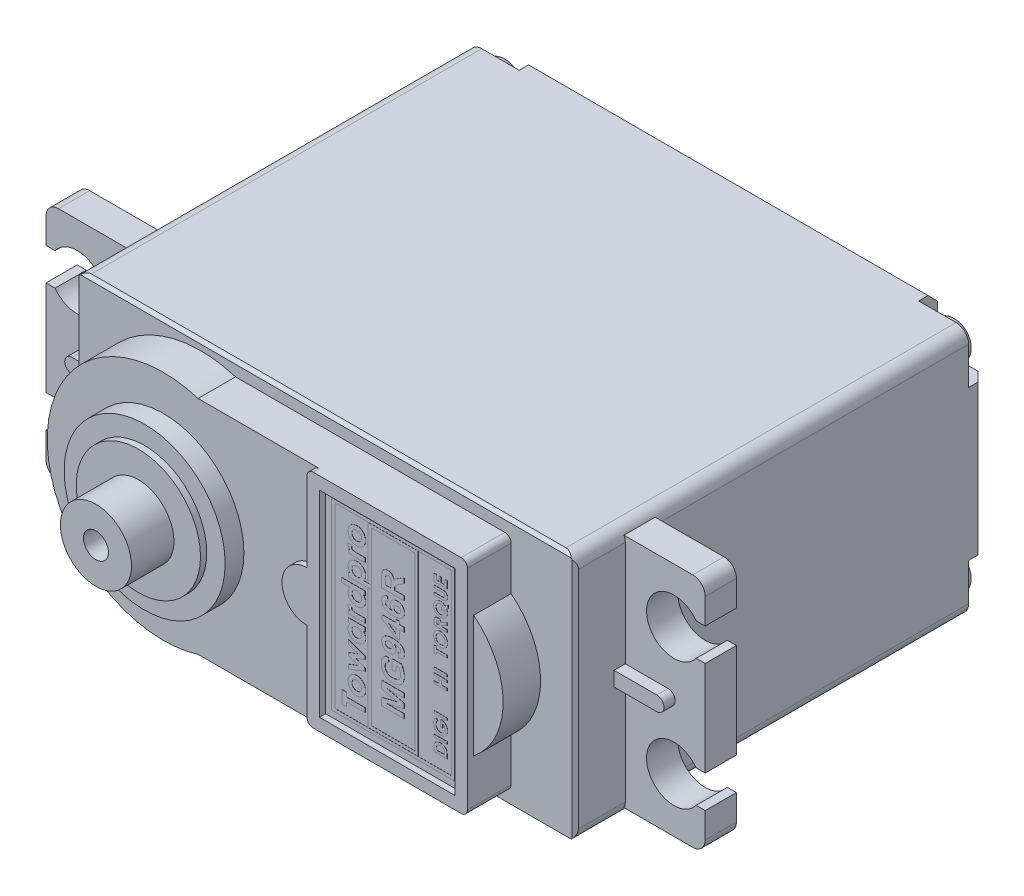
SolidWorks part; units mm, degrees
ref_plane "Front Plane" through (0, 0, 0) normal (0, 0, 1) x (1, 0, 0)
ref_plane "Top Plane" through (0, 0, 0) normal (0, 1, 0) x (1, 0, 0)
ref_plane "Right Plane" through (0, 0, 0) normal (1, 0, 0) x (0, 0, -1)
ref_plane "Plane1" through (0, -10, 0) normal (0, -1, 0) x (1, 0, 0)
sketch "Sketch1" plane through (0, -10, 0) normal (0, -1, 0) x (1, 0, 0)
  line L0 (-20, 16.5) -> (-20, -16.5)
  line L1 (-20, -16.5) -> (20, -16.5)
  line L2 (20, -16.5) -> (20, 16.5)
  line L3 (20, 16.5) -> (-20, 16.5)
extrude "Boss-Extrude1" add sketch "Sketch1" against normal blind 20
sketch "Sketch2" plane through (0, 0, 16.5) normal (0, 0, 1) x (1, 0, 0)
  line L0 (14.8541, 8.875) -> (14.8541, -8.875)
  line L1 (14.8541, -8.875) -> (-7.2207, -8.875)
  line L2 (-7.2207, 8.875) -> (14.8541, 8.875)
  arc A0 (-7.2207, -8.875) -> (-7.2207, 8.875) centre (-10, 0) cw
extrude "Boss-Extrude2" add sketch "Sketch2" along normal blind 3
sketch "Sketch3" plane through (0, 0, 19.5) normal (0, 0, 1) x (1, 0, 0)
  line L0 (2.0041, 8.875) -> (14.8541, 8.875)
  line L1 (14.8541, 8.875) -> (14.8541, -8.875)
  line L2 (14.8541, -8.875) -> (2.0041, -8.875)
  line L3 (2.0041, -8.875) -> (2.0041, 8.875)
extrude "Boss-Extrude3" add sketch "Sketch3" along normal blind 0.5
sketch "Sketch4" plane through (0, 0, 19.5) normal (0, 0, 1) x (1, 0, 0)
  line L0 (2.0041, 2) -> (2.0041, -2)
  arc A0 (2.0041, -2) -> (2.0041, 2) centre (2.0041, 0) cw
extrude "Boss-Extrude4" add sketch "Sketch4" along normal blind 0.5
sketch "Sketch5" plane through (-20, 0, 0) normal (-1, 0, 0) x (0, 0, 1)
  line L0 (10, 9.45) -> (12.5, 9.45)
  line L1 (12.5, 9.45) -> (12.5, -9.45)
  line L2 (12.5, -9.45) -> (10, -9.45)
  line L3 (10, -9.45) -> (10, 9.45)
extrude "Boss-Extrude5" add sketch "Sketch5" along normal blind 6.4
sketch "Sketch6" plane through (0, 0, 10) normal (0, 0, -1) x (-1, 0, 0)
  line L0 (26.4, 6.4) -> (25.6748, 6.4)
  line L1 (25.6748, 3.8) -> (26.4, 3.8)
  line L2 (26.4, 3.8) -> (26.4, 6.4)
  arc A0 (25.6748, 6.4) -> (25.6748, 3.8) centre (23.9, 5.1) cw
extrude "Cut-Extrude1" cut sketch "Sketch6" against normal through all
sketch "Sketch7" plane through (0, 0, 10) normal (0, 0, -1) x (-1, 0, 0)
  line L0 (26.4, -3.8) -> (25.6748, -3.8)
  line L1 (25.6748, -6.4) -> (26.4, -6.4)
  line L2 (26.4, -6.4) -> (26.4, -3.8)
  arc A0 (25.6748, -3.8) -> (25.6748, -6.4) centre (23.9, -5.1) cw
extrude "Cut-Extrude2" cut sketch "Sketch7" against normal through all
sketch "Sketch8" plane through (20, 0, 0) normal (1, 0, 0) x (0, 0, -1)
  line L0 (-10, -9.45) -> (-12.5, -9.45)
  line L1 (-12.5, -9.45) -> (-12.5, 9.45)
  line L2 (-12.5, 9.45) -> (-10, 9.45)
  line L3 (-10, 9.45) -> (-10, -9.45)
extrude "Boss-Extrude6" add sketch "Sketch8" along normal blind 6.4
sketch "Sketch9" plane through (0, 0, 12.5) normal (0, 0, 1) x (1, 0, 0)
  line L0 (26.4, 3.8) -> (26.4, 6.4)
  line L1 (26.4, 6.4) -> (25.6748, 6.4)
  line L2 (25.6748, 3.8) -> (26.4, 3.8)
  arc A0 (25.6748, 6.4) -> (25.6748, 3.8) centre (23.9, 5.1) cw
extrude "Cut-Extrude3" cut sketch "Sketch9" against normal through all
sketch "Sketch10" plane through (0, 0, 12.5) normal (0, 0, 1) x (1, 0, 0)
  line L0 (26.4, -6.4) -> (26.4, -3.8)
  line L1 (26.4, -3.8) -> (25.6748, -3.8)
  line L2 (25.6748, -6.4) -> (26.4, -6.4)
  arc A0 (25.6748, -3.8) -> (25.6748, -6.4) centre (23.9, -5.1) cw
extrude "Cut-Extrude4" cut sketch "Sketch10" against normal through all
sketch "Sketch11" plane through (0, 0, 12.5) normal (0, 0, 1) x (1, 0, 0)
  line L0 (-23.42, 0.58) -> (-20, 0.58)
  line L1 (-20, 0.58) -> (-20, -0.58)
  line L2 (-20, -0.58) -> (-23.42, -0.58)
  arc A0 (-23.42, -0.58) -> (-23.42, 0.58) centre (-23.42, 0) cw
extrude "Boss-Extrude7" add sketch "Sketch11" along normal blind 0.9
sketch "Sketch12" plane through (0, 10, 0) normal (0, 1, 0) x (-1, 0, 0)
  line L0 (-16, -16.5) -> (-16, -15)
  line L1 (-16, -15) -> (-20, -15)
  line L2 (-20, -15) -> (-20, -16.5)
  line L3 (-20, -16.5) -> (-16, -16.5)
extrude "Cut-Extrude5" cut sketch "Sketch12" against normal blind 4
sketch "Sketch13" plane through (-20, 0, 0) normal (-1, 0, 0) x (0, 0, 1)
  line L0 (-16.5, 6) -> (-15, 6)
  line L1 (-15, 6) -> (-15, 10)
  line L2 (-15, 10) -> (-16.5, 10)
  line L3 (-16.5, 10) -> (-16.5, 6)
extrude "Cut-Extrude6" cut sketch "Sketch13" against normal blind 4
sketch "Sketch14" plane through (-20, 0, 0) normal (-1, 0, 0) x (0, 0, 1)
  line L0 (-16.5, -10) -> (-15, -10)
  line L1 (-15, -10) -> (-15, -6)
  line L2 (-15, -6) -> (-16.5, -6)
  line L3 (-16.5, -6) -> (-16.5, -10)
extrude "Cut-Extrude7" cut sketch "Sketch14" against normal blind 4
sketch "Sketch15" plane through (0, -10, 0) normal (0, -1, 0) x (1, 0, 0)
  line L0 (20, -16.5) -> (20, -15)
  line L1 (20, -15) -> (16, -15)
  line L2 (16, -15) -> (16, -16.5)
  line L3 (16, -16.5) -> (20, -16.5)
extrude "Cut-Extrude8" cut sketch "Sketch15" against normal blind 4
sketch "Sketch16" plane through (0, 0, 12.5) normal (0, 0, 1) x (1, 0, 0)
  line L0 (23.42, -0.58) -> (20, -0.58)
  line L1 (20, -0.58) -> (20, 0.58)
  line L2 (20, 0.58) -> (23.42, 0.58)
  arc A0 (23.42, 0.58) -> (23.42, -0.58) centre (23.42, 0) cw
extrude "Boss-Extrude8" add sketch "Sketch16" along normal blind 0.9
sketch "Sketch17" plane through (0, 0, 16.5) normal (0, 0, 1) x (1, 0, 0)
  line L0 (14.8541, -4.875) -> (14.8541, 4.875)
  arc A0 (14.8541, 4.875) -> (14.8541, -4.875) centre (11, 0) cw
extrude "Boss-Extrude9" add sketch "Sketch17" along normal blind 3
sketch "Sketch18" plane through (0, 0, 20) normal (0, 0, 1) x (1, 0, 0)
  line L0 (13.8541, 7.875) -> (3.0041, 7.875)
  line L1 (3.0041, 7.875) -> (3.0041, -7.875)
  line L2 (3.0041, -7.875) -> (13.8541, -7.875)
  line L3 (13.8541, -7.875) -> (13.8541, 7.875)
extrude "Cut-Extrude9" cut sketch "Sketch18" against normal blind 0.5
sketch "Sketch19" plane through (0, 0, 0) normal (0, 1, 0) x (1, 0, 0)
  line L0 (-3.55, -19.5) -> (-10, -19.5)
  line L1 (-10, -19.5) -> (-10, -24.9)
  line L2 (-10, -24.9) -> (-7.15, -24.9)
  line L3 (-7.15, -24.9) -> (-7.15, -21.5)
  line L4 (-7.15, -21.5) -> (-5.025, -21.5)
  line L5 (-5.025, -21.5) -> (-5.025, -21)
  line L6 (-5.025, -21) -> (-3.55, -21)
  line L7 (-3.55, -21) -> (-3.55, -19.5)
  line L8 (-10, -19.5) -> (-10, -24.9) construction
revolve "Revolve1" add sketch "Sketch19" angle 360 about L8 reverse direction yes
ref_plane "Plane2" through (0, -5.1, 0) normal (0, -1, 0) x (1, 0, 0)
sketch "Sketch20" plane through (0, -5.1, 0) normal (0, -1, 0) x (1, 0, 0)
  line L0 (26.1, 12.5) -> (23.9, 12.5)
  line L1 (23.9, 12.5) -> (23.9, 10)
  line L2 (23.9, 10) -> (26.1, 10)
  line L3 (26.1, 10) -> (26.1, 12.5)
  line L4 (23.9, 12.5) -> (23.9, 10) construction
revolve "Cut-Revolve1" cut sketch "Sketch20" angle 360 about L4 reverse direction yes
ref_plane "Plane3" through (0, 5.1, 0) normal (0, -1, 0) x (1, 0, 0)
sketch "Sketch21" plane through (0, 5.1, 0) normal (0, -1, 0) x (1, 0, 0)
  line L0 (26.1, 12.5) -> (23.9, 12.5)
  line L1 (23.9, 12.5) -> (23.9, 10)
  line L2 (23.9, 10) -> (26.1, 10)
  line L3 (26.1, 10) -> (26.1, 12.5)
  line L4 (23.9, 12.5) -> (23.9, 10) construction
revolve "Cut-Revolve2" cut sketch "Sketch21" angle 360 about L4 reverse direction yes
sketch "Sketch22" plane through (0, 5.1, 0) normal (0, -1, 0) x (1, 0, 0)
  line L0 (-21.7, 12.5) -> (-23.9, 12.5)
  line L1 (-23.9, 12.5) -> (-23.9, 10)
  line L2 (-23.9, 10) -> (-21.7, 10)
  line L3 (-21.7, 10) -> (-21.7, 12.5)
  line L4 (-23.9, 12.5) -> (-23.9, 10) construction
revolve "Cut-Revolve3" cut sketch "Sketch22" angle 360 about L4 reverse direction yes
sketch "Sketch23" plane through (0, -5.1, 0) normal (0, -1, 0) x (1, 0, 0)
  line L0 (-21.7, 12.5) -> (-23.9, 12.5)
  line L1 (-23.9, 12.5) -> (-23.9, 10)
  line L2 (-23.9, 10) -> (-21.7, 10)
  line L3 (-21.7, 10) -> (-21.7, 12.5)
  line L4 (-23.9, 12.5) -> (-23.9, 10) construction
  dimension "D1" = 2.2
revolve "Cut-Revolve4" cut sketch "Sketch23" angle 360 about L4 reverse direction yes
hole_wizard "Ø2.0 (2) Diameter Hole1" positions "Sketch25" profile "Sketch24" hole size "Ø2.0" standard "ANSI Metric"
sketch "Sketch25" plane through (0, 0, 24.9) normal (0, 0, 1) x (1, 0, 0)
  point P0 (-10, 0)
sketch "Sketch24" plane through (-10, 0, 24.9) normal (1, 0, 0) x (0, -1, 0)
  line L0 (0, 0) -> (0, 3.4)
  line L1 (0, 3.4) -> (1, 3.4)
  line L2 (1, 3.4) -> (1, 0)
  line L5 (1, 0) -> (0, 0)
  line L10 (0, 3.4) -> (-1, 3.4) construction
  line L11 (0, -6.35) -> (0, 107.95) construction
  dimension "Hole Dia." = 2
  dimension "Hole Depth" = 3.4
  dimension "Drill Angle" = 180
hole_wizard "Ø1.8 (1.8) Diameter Hole1" positions "Sketch27" profile "Sketch26" hole size "Ø1.8" standard "ANSI Metric"
sketch "Sketch27" plane through (0, 0, -15) normal (0, 0, -1) x (-1, 0, 0)
  point P0 (-18, 8)
  point P1 (18, 8)
  point P2 (18, -8)
  point P3 (-18, -8)
sketch "Sketch26" plane through (18, 8, -15) normal (1, 0, 0) x (0, 1, 0)
  line L0 (0, 0) -> (0, 8.5408)
  line L1 (0, 8.5408) -> (0.9, 8)
  line L2 (0.9, 8) -> (0.9, 0)
  line L5 (0.9, 0) -> (0, 0)
  line L10 (0, 8.5408) -> (-0.9, 8) construction
  line L11 (0, -6.35) -> (0, 107.95) construction
  dimension "Hole Dia." = 1.8
  dimension "Hole Depth" = 8
  dimension "Drill Angle" = 118
chamfer "Chamfer1" distance 0.25 angle 45 4 edges at (20, 0, 16.5) (0, 10, 16.5) (-20, 0, 16.5) (0, -10, 16.5)
chamfer "Chamfer2" distance 0.75 angle 45 4 edges at (0, 10, -16.5) (20, 0, -16.5) (0, -10, -16.5) (-20, 0, -16.5)
fillet "Fillet1" radius 0.5 4 edges at (14.8541, -8.875, 18.25) (14.8541, 8.875, 18.25) tangent propagation no
fillet "Fillet2" radius 1 8 edges at (20, 10, 0.625) (20, -10, 0.625) (26.4, 9.45, 11.25) (-20, -10, 0.625) (26.4, -9.45, 11.25) (-26.4, -9.45, 11.25) (-26.4, 9.45, 11.25) (-20, 10, 0.625) tangent propagation no
fillet "Fillet3" radius 2 4 edges at (-16, 6, -15.75) (16, 6, -15.75) (-16, -6, -15.75) (16, -6, -15.75) tangent propagation no
sketch "Sketch28" plane through (0, 0, 19.5) normal (0, 0, 1) x (1, 0, 0)
  line L1 (3.0041, -7.875) -> (13.8541, -7.875)
  line L2 (3.0041, -7.875) -> (3.0041, 7.875)
  line L3 (3.0041, 7.875) -> (13.8541, 7.875)
  line L4 (13.8541, -7.875) -> (13.8541, 7.875)
extrude "Boss-Extrude10" add sketch "Sketch28" along normal blind 0.01
sketch "Sketch29" plane through (0, 0, 19.51) normal (0, 0, 1) x (1, 0, 0)
  line L0 (6.8665, -7.875) -> (6.8665, -7.375) construction
  line L1 (3.0041, -7.875) -> (13.8541, -7.875) construction
  line L2 (3.0041, 1.859) -> (3.5041, 1.859) construction
  line L3 (3.0041, 7.875) -> (3.0041, -7.875) construction
  line L4 (10.2846, 7.875) -> (10.2846, 7.375) construction
  line L5 (13.8541, 7.875) -> (3.0041, 7.875) construction
  line L6 (13.8541, -1.5785) -> (13.3541, -1.5785) construction
  line L7 (13.8541, -7.875) -> (13.8541, 7.875) construction
  line L8 (3.7541, 7.125) -> (13.1041, 7.125)
  line L9 (3.5041, -7.375) -> (13.3541, -7.375)
  line L10 (3.5041, -7.375) -> (3.5041, 7.375)
  line L11 (3.5041, 7.375) -> (13.3541, 7.375)
  line L12 (13.3541, -7.375) -> (13.3541, 7.375)
  line L13 (13.1041, -7.125) -> (13.1041, 7.125)
  line L14 (3.7541, -7.125) -> (13.1041, -7.125)
  line L15 (3.7541, -7.125) -> (3.7541, 7.125)
  line L16 (8.4291, -7.125) -> (8.4291, -7.115) construction
  line L17 (8.4291, -7.115) -> (6.4291, -7.115) construction
  line L18 (8.4291, -4.0034) -> (10.4291, -4.0034) construction
  line L19 (9.3693, 7.125) -> (9.3693, 7.115) construction
  line L20 (10.4291, -4.0034) -> (10.4291, 6.8709) construction
  line L21 (6.6791, -6.865) -> (6.6791, 6.865)
  line L22 (6.4291, -7.115) -> (10.4291, -7.115)
  line L23 (6.4291, -7.115) -> (6.4291, 7.115)
  line L24 (6.4291, 7.115) -> (10.4291, 7.115)
  line L25 (10.4291, -7.115) -> (10.4291, 7.115)
  line L26 (6.6791, 6.865) -> (10.1791, 6.865)
  line L27 (10.1791, -6.865) -> (10.1791, 6.865)
  line L28 (6.6791, -6.865) -> (10.1791, -6.865)
  dimension "D1" = 0.25
  dimension "D2" = 0.25
extrude "Boss-Extrude11" add sketch "Sketch29" along normal blind 0.01 contours L22 L25 L24 L23 L28 L21 L26 L27 | L9 L12 L11 L10 L14 L15 L8 L13 region at (3.6815, 0, 19.51) region at (6.5769, 0, 19.51)
sketch "Sketch30" plane through (0, 0, 19.51) normal (0, 0, 1) x (1, 0, 0)
  line L0 (9.3092, -6.0531) -> (9.3092, 5.5838) construction
  line L1 (12.7516, 6.631) -> (12.7516, -6.6636) construction
  line L2 (6.1944, -6.6636) -> (6.1944, 6.8512) construction
  text T0 "<b>Towardpro</b>" font "Century Gothic" height in points 7
  text T1 "<b>DIGI    HI  TORQUE</b>" font "Century Gothic" height in points 4
  text T2 "MG946R" font "Arial" height in points 7
extrude "Boss-Extrude12" add sketch "Sketch30" along normal blind 0.015
sketch "Sketch31" plane through (0, 0, -15) normal (0, 0, -1) x (-1, 0, 0)
  circle A0 centre (18, 8) radius 1.5
  circle A1 centre (18, -8) radius 1.5
  circle A2 centre (-18, 8) radius 1.5
  circle A3 centre (-18, -8) radius 1.5
extrude "Boss-Extrude13" add sketch "Sketch31" along normal blind 1
fillet "Fillet5" radius 0.5 4 edges at (-19.5, 8, -16) (-19.5, -8, -16) (16.5, -8, -16) (16.5, 8, -16)
sketch "Sketch32" plane through (0, 0, -16) normal (0, 0, -1) x (-1, 0, 0)
  line L0 (19, 8) -> (19, 8.5) construction
  line L1 (17, 8) -> (17, 7.5) construction
  line L2 (18, 9) -> (17.5, 9) construction
  line L3 (18, 7) -> (18.5, 7) construction
  line L4 (19, 8.5) -> (19, 7.5)
  line L5 (19, 7.5) -> (18.5, 7.5)
  line L6 (18.5, 7.5) -> (18.5, 7)
  line L7 (18.5, 7) -> (17.5, 7)
  line L8 (17.5, 7) -> (17.5, 7.5)
  line L9 (17.5, 7.5) -> (17, 7.5)
  line L10 (17, 7.5) -> (17, 8.5)
  line L11 (17, 8.5) -> (17.5, 8.5)
  line L12 (17.5, 8.5) -> (17.5, 9)
  line L13 (17.5, 9) -> (18.5, 9)
  line L14 (18.5, 9) -> (18.5, 8.5)
  line L15 (18.5, 8.5) -> (19, 8.5)
  line L16 (19, -8) -> (19, -8.5) construction
  line L17 (17, -8) -> (17, -7.5) construction
  line L18 (18, -7) -> (17.5, -7) construction
  line L19 (18, -9) -> (18.5, -9) construction
  line L20 (-17, -8) -> (-17, -7.5) construction
  line L21 (-18, -7) -> (-18.5, -7) construction
  line L22 (-18, -9) -> (-17.5, -9) construction
  line L23 (-19, -8) -> (-19, -8.5) construction
  line L24 (-17, -7.5) -> (-17, -8.5)
  line L25 (-17, -8.5) -> (-17.5, -8.5)
  line L26 (-17.5, -8.5) -> (-17.5, -9)
  line L27 (-17.5, -9) -> (-18.5, -9)
  line L28 (-18.5, -9) -> (-18.5, -8.5)
  line L29 (-18.5, -8.5) -> (-19, -8.5)
  line L30 (-19, -8.5) -> (-19, -7.5)
  line L31 (-19, -7.5) -> (-18.5, -7.5)
  line L32 (-18.5, -7.5) -> (-18.5, -7)
  line L33 (-18.5, -7) -> (-17.5, -7)
  line L34 (-17.5, -7) -> (-17.5, -7.5)
  line L35 (-17.5, -7.5) -> (-17, -7.5)
  line L36 (19, -7.5) -> (19, -8.5)
  line L37 (19, -8.5) -> (18.5, -8.5)
  line L38 (18.5, -8.5) -> (18.5, -9)
  line L39 (18.5, -9) -> (17.5, -9)
  line L40 (17.5, -9) -> (17.5, -8.5)
  line L41 (17.5, -8.5) -> (17, -8.5)
  line L42 (17, -8.5) -> (17, -7.5)
  line L43 (17, -7.5) -> (17.5, -7.5)
  line L44 (17.5, -7.5) -> (17.5, -7)
  line L45 (17.5, -7) -> (18.5, -7)
  line L46 (18.5, -7) -> (18.5, -7.5)
  line L47 (18.5, -7.5) -> (19, -7.5)
  line L48 (-17, 8.5) -> (-17, 7.5)
  line L49 (-17, 7.5) -> (-17.5, 7.5)
  line L50 (-17.5, 7.5) -> (-17.5, 7)
  line L51 (-17.5, 7) -> (-18.5, 7)
  line L52 (-18.5, 7) -> (-18.5, 7.5)
  line L53 (-18.5, 7.5) -> (-19, 7.5)
  line L54 (-19, 7.5) -> (-19, 8.5)
  line L55 (-19, 8.5) -> (-18.5, 8.5)
  line L56 (-18.5, 8.5) -> (-18.5, 9)
  line L57 (-18.5, 9) -> (-17.5, 9)
  line L58 (-17.5, 9) -> (-17.5, 8.5)
  line L59 (-17.5, 8.5) -> (-17, 8.5)
  circle A0 centre (18, 8) radius 1 construction
  circle A1 centre (18, -8) radius 1 construction
  circle A2 centre (-18, -8) radius 1 construction
extrude "Cut-Extrude10" cut sketch "Sketch32" against normal blind 0.7
chamfer "Chamfer3" distance 0.6 angle 35 48 edges at (17, 8, -15.3) (17.25, 7.5, -15.3) (17.5, 7.25, -15.3) (18, 7, -15.3) (18.5, 7.25, -15.3) (18.75, 7.5, -15.3) (19, 8, -15.3) (18.75, 8.5, -15.3) (18.5, 8.75, -15.3) (18, 9, -15.3) (17.5, 8.75, -15.3) (17.25, 8.5, -15.3) (17, -8, -15.3) (17.25, -8.5, -15.3) (17.5, -8.75, -15.3) (18, -9, -15.3) (18.5, -8.75, -15.3) (18.75, -8.5, -15.3) (19, -8, -15.3) (18.75, -7.5, -15.3) (18.5, -7.25, -15.3) (18, -7, -15.3) (17.5, -7.25, -15.3) (17.25, -7.5, -15.3) (-18.5, -8.75, -15.3) (-18, -9, -15.3) (-17.5, -8.75, -15.3) (-17.25, -8.5, -15.3) (-17, -8, -15.3) (-17.25, -7.5, -15.3) (-17.5, -7.25, -15.3) (-18, -7, -15.3) (-18.5, -7.25, -15.3) (-18.75, -7.5, -15.3) (-19, -8, -15.3) (-18.75, -8.5, -15.3) (-19, 8, -15.3) (-18.75, 7.5, -15.3) (-18.5, 7.25, -15.3) (-18, 7, -15.3) (-17.5, 7.25, -15.3) (-17.25, 7.5, -15.3) (-17, 8, -15.3) (-17.25, 8.5, -15.3) (-17.5, 8.75, -15.3) (-18, 9, -15.3) (-18.5, 8.75, -15.3) (-18.75, 8.5, -15.3) first distance on face at (17, 8.155, -15.4045) first distance on face at (17.2402, 7.5, -15.7186) first distance on face at (17.5, 7.2134, -15.7158) first distance on face at (17.845, 7, -15.4045) first distance on face at (18.5, 7.2402, -15.7186) first distance on face at (18.7866, 7.5, -15.7158) first distance on face at (19, 7.845, -15.4045) first distance on face at (18.7598, 8.5, -15.7186) first distance on face at (18.5, 8.7866, -15.7158) first distance on face at (18.155, 9, -15.4045) first distance on face at (17.5, 8.7598, -15.7186) first distance on face at (17.2134, 8.5, -15.7158) first distance on face at (17, -7.845, -15.4045) first distance on face at (17.2402, -8.5, -15.7186) first distance on face at (17.5, -8.7866, -15.7158) first distance on face at (17.845, -9, -15.4045) first distance on face at (18.5, -8.7598, -15.7186) first distance on face at (18.7866, -8.5, -15.7158) first distance on face at (19, -8.155, -15.4045) first distance on face at (18.7598, -7.5, -15.7186) first distance on face at (18.5, -7.2134, -15.7158) first distance on face at (18.155, -7, -15.4045) first distance on face at (17.5, -7.2402, -15.7186) first distance on face at (17.2134, -7.5, -15.7158) first distance on face at (-18.5, -8.7866, -15.7158) first distance on face at (-18.155, -9, -15.4045) first distance on face at (-17.5, -8.7598, -15.7186) first distance on face at (-17.2134, -8.5, -15.7158) first distance on face at (-17, -8.155, -15.4045) first distance on face at (-17.2402, -7.5, -15.7186) first distance on face at (-17.5, -7.2134, -15.7158) first distance on face at (-17.845, -7, -15.4045) first distance on face at (-18.5, -7.2402, -15.7186) first distance on face at (-18.7866, -7.5, -15.7158) first distance on face at (-19, -7.845, -15.4045) first distance on face at (-18.7598, -8.5, -15.7186) first distance on face at (-19, 8.155, -15.4045) first distance on face at (-18.7598, 7.5, -15.7186) first distance on face at (-18.5, 7.2134, -15.7158) first distance on face at (-18.155, 7, -15.4045) first distance on face at (-17.5, 7.2402, -15.7186) first distance on face at (-17.2134, 7.5, -15.7158) first distance on face at (-17, 7.845, -15.4045) first distance on face at (-17.2402, 8.5, -15.7186) first distance on face at (-17.5, 8.7866, -15.7158) first distance on face at (-17.845, 9, -15.4045) first distance on face at (-18.5, 8.7598, -15.7186) first distance on face at (-18.7866, 8.5, -15.7158)
fillet "Fillet8" radius 0.1 48 edges at (17.9201, 7.6701, -15.3) (18, 7.4201, -15.3) (18.0799, 7.6701, -15.3) (18.3299, 7.9201, -15.3) (18.5799, 8, -15.3) (18.3299, 8.0799, -15.3) (18.0799, 8.3299, -15.3) (18, 8.5799, -15.3) (17.9201, 8.3299, -15.3) (17.6701, 8.0799, -15.3) (17.4201, 8, -15.3) (17.6701, 7.9201, -15.3) (17.9201, -8.3299, -15.3) (18, -8.5799, -15.3) (18.0799, -8.3299, -15.3) (18.3299, -8.0799, -15.3) (18.5799, -8, -15.3) (18.3299, -7.9201, -15.3) (18.0799, -7.6701, -15.3) (18, -7.4201, -15.3) (17.9201, -7.6701, -15.3) (17.6701, -7.9201, -15.3) (17.4201, -8, -15.3) (17.6701, -8.0799, -15.3) (-17.9201, -8.3299, -15.3) (-17.6701, -8.0799, -15.3) (-17.4201, -8, -15.3) (-17.6701, -7.9201, -15.3) (-17.9201, -7.6701, -15.3) (-18, -7.4201, -15.3) (-18.0799, -7.6701, -15.3) (-18.3299, -7.9201, -15.3) (-18.5799, -8, -15.3) (-18.3299, -8.0799, -15.3) (-18.0799, -8.3299, -15.3) (-18, -8.5799, -15.3) (-18.0799, 7.6701, -15.3) (-18, 7.4201, -15.3) (-17.9201, 7.6701, -15.3) (-17.6701, 7.9201, -15.3) (-17.4201, 8, -15.3) (-17.6701, 8.0799, -15.3) (-17.9201, 8.3299, -15.3) (-18, 8.5799, -15.3) (-18.0799, 8.3299, -15.3) (-18.3299, 8.0799, -15.3) (-18.5799, 8, -15.3) (-18.3299, 7.9201, -15.3)
